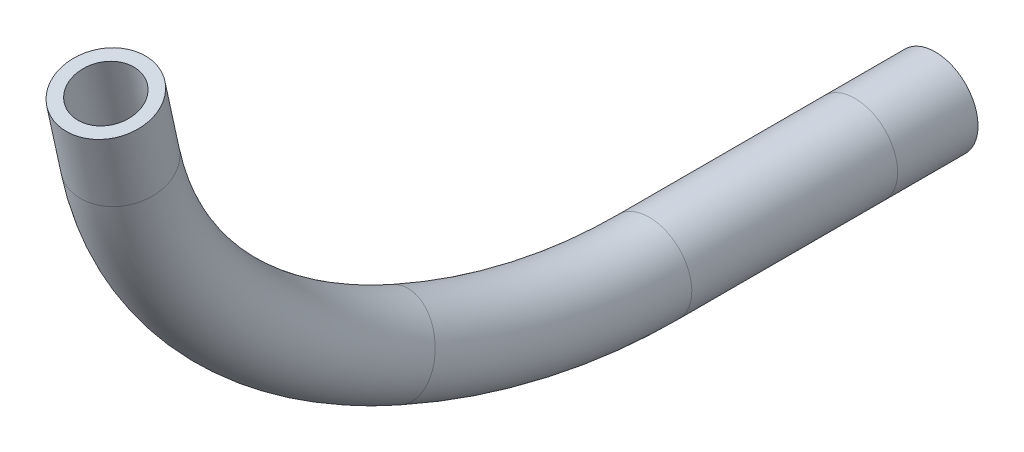
SolidWorks part; units mm, degrees
material "Silicon Rubber"
ref_plane "X-Y Datum" through (0, 0, 0) normal (0, 0, 1) x (1, 0, 0)
ref_plane "X-Z Datum" through (0, 0, 0) normal (0, 1, 0) x (1, 0, 0)
ref_plane "Y-Z Datum" through (0, 0, 0) normal (1, 0, 0) x (0, 0, -1)
sketch3d "3DSketch1"
  line L0 (0, 0, 0) -> (0, 0, -25.4)
  line L2 (0, 0, 0) -> (0, 0, 65.0083)
  line L3 (-10.1494, 122.9488, 226.48) -> (-11.7056, 100.7587, 220.4098)
  arc A4 (-5.8646, 12.6408, 138.9609) -> (0, 0, 65.0083) centre (-85.5172, 184.3286, 65.0083) ccw
  circle A8 centre (-11.7056, 100.7587, 220.4098) radius 7.5 construction
  circle A9 centre (-11.7056, 100.7587, 220.4098) radius 7.5 construction
  circle A10 centre (-10.1494, 122.9488, 226.48) radius 10 construction
  circle A11 centre (-10.1494, 122.9488, 226.48) radius 10 construction
  arc A14 (-11.7056, 100.7587, 220.4098) -> (-5.8646, 12.6408, 138.9609) centre (17.316, 131.4846, 100.6489) ccw
  point P4 (140.6581, 115.7618, 126.5045)
  point P7 (-11.1994, 107.9764, 222.3842)
  point P10 (-11.1994, 107.9764, 222.3842)
  point P13 (-9.4745, 132.5724, 229.1126)
  point P16 (98.8114, 269.8459, 65.0083)
  point P18 (-9.4745, 132.5724, 229.1126)
  dimension "D3" = 203.2
  dimension "D2" = 127
  dimension "D1" = 25.4
sweep "Sweep1" add path "3DSketch1" circular profile diameter 26.9875 parameters "D3"=26.9875
sweep "Cut-Sweep1" cut path "3DSketch1<2>" circular profile diameter 19.05 parameters "D3"=19.05
sketch3d "3DSketch1<2>" same geometry as "3DSketch1"
